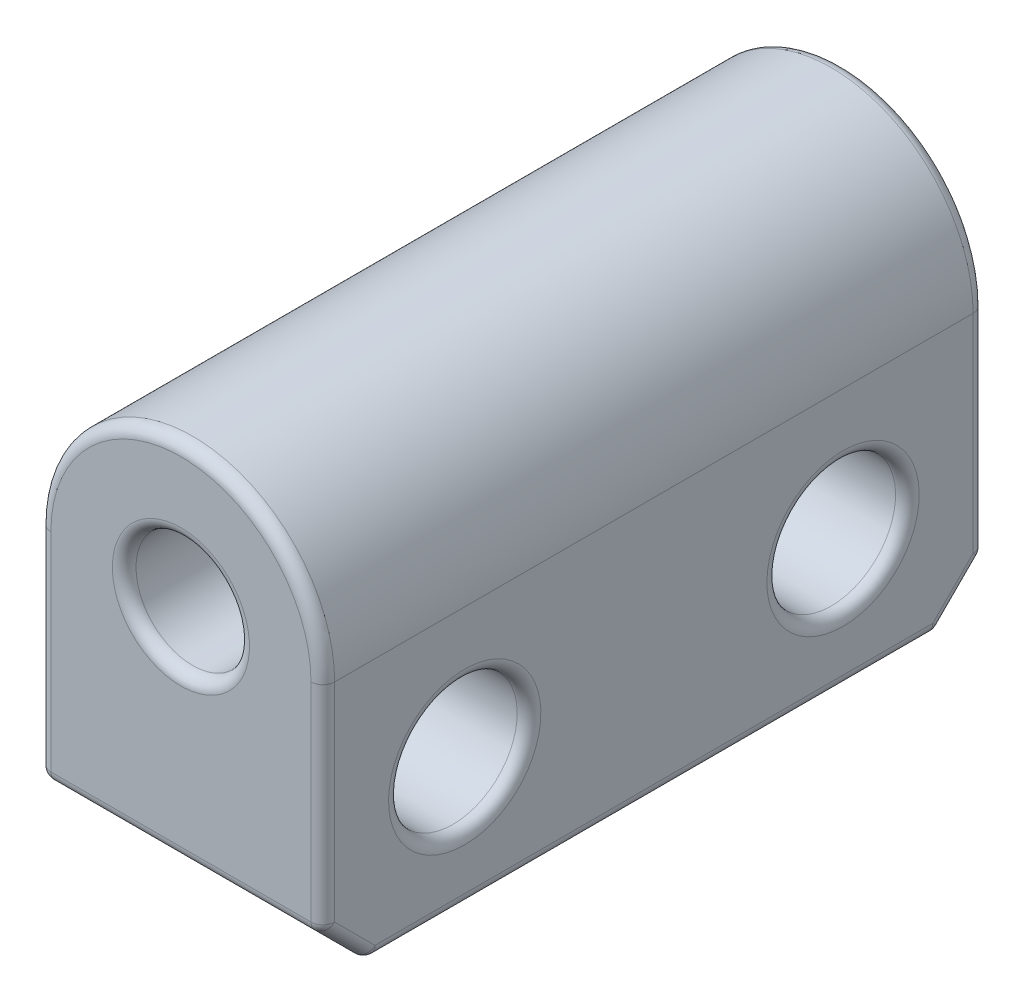
SolidWorks part; units mm, degrees
ref_plane "Front Plane" through (0, 0, 0) normal (0, 0, 1) x (1, 0, 0)
ref_plane "Top Plane" through (0, 0, 0) normal (0, 1, 0) x (1, 0, 0)
ref_plane "Right Plane" through (0, 0, 0) normal (1, 0, 0) x (0, 0, -1)
sketch "Sketch1" plane through (0, 0, 0) normal (0, 0, 1) x (1, 0, 0)
  line L0 (-4.7625, 0) -> (-4.7625, -8.7312)
  line L1 (-4.7625, -8.7312) -> (4.7625, -8.7312)
  line L2 (4.7625, -8.7312) -> (4.7625, 0)
  arc A1 (-4.7625, 0) -> (4.7625, 0) centre (0, 0) cw
  circle A2 centre (0, 0) radius 1.905
  dimension "D1" = 3.81
  dimension "D2" = 9.525
  dimension "D3" = 8.7312
extrude "Boss-Extrude1" add sketch "Sketch1" along normal mid plane 22.225
sketch "Sketch3" plane through (0, 0, 0) normal (0, 0, 1) x (1, 0, 0)
  circle A0 centre (0, 0) radius 1.905 construction
  circle A1 centre (0, 0) radius 1.905
extrude "Boss-Extrude2" add sketch "Sketch3" along normal mid plane 3.9688
sketch "Sketch2" plane through (-4.7625, 0, 0) normal (-1, 0, 0) x (0, 0, 1)
  line L0 (-6.35, -4.3656) -> (6.35, -4.3656) construction
  circle A0 centre (-6.35, -4.3656) radius 2.159
  circle A1 centre (6.35, -4.3656) radius 2.159
  point P4 (0, -4.3656)
  dimension "D2" = 4.318
  dimension "D3" = 4.3656
  dimension "D1" = 12.7
extrude "Cut-Extrude1" cut sketch "Sketch2" against normal through all
chamfer "Chamfer2" distance 1.5875 angle 45 2 edges at (0, -8.7312, 11.1125) (0, -8.7312, -11.1125)
fillet "Fillet2" radius 0.3969 22 edges at (0, -7.1438, -11.1125) (-4.7625, -7.9375, 10.3187) (-4.7625, -7.9375, -10.3188) (0, -8.7312, 9.525) (0, -8.7312, -9.525) (4.7625, -7.9375, 10.3187) (4.7625, -7.9375, -10.3188) (0, -7.1438, 11.1125) (-4.7625, -8.7312, 0) (4.7625, -8.7312, 0) (4.7625, -3.5719, 11.1125) (-4.7625, -3.5719, 11.1125) (0, 4.7625, 11.1125) (4.7625, -3.5719, -11.1125) (-4.7625, -3.5719, -11.1125) (0, 4.7625, -11.1125) (4.7625, -6.5246, -6.35) (-4.7625, -6.5246, -6.35) (-4.7625, -6.5246, 6.35) (4.7625, -6.5246, 6.35) (1.905, 0, 11.1125) (1.905, 0, -11.1125)
